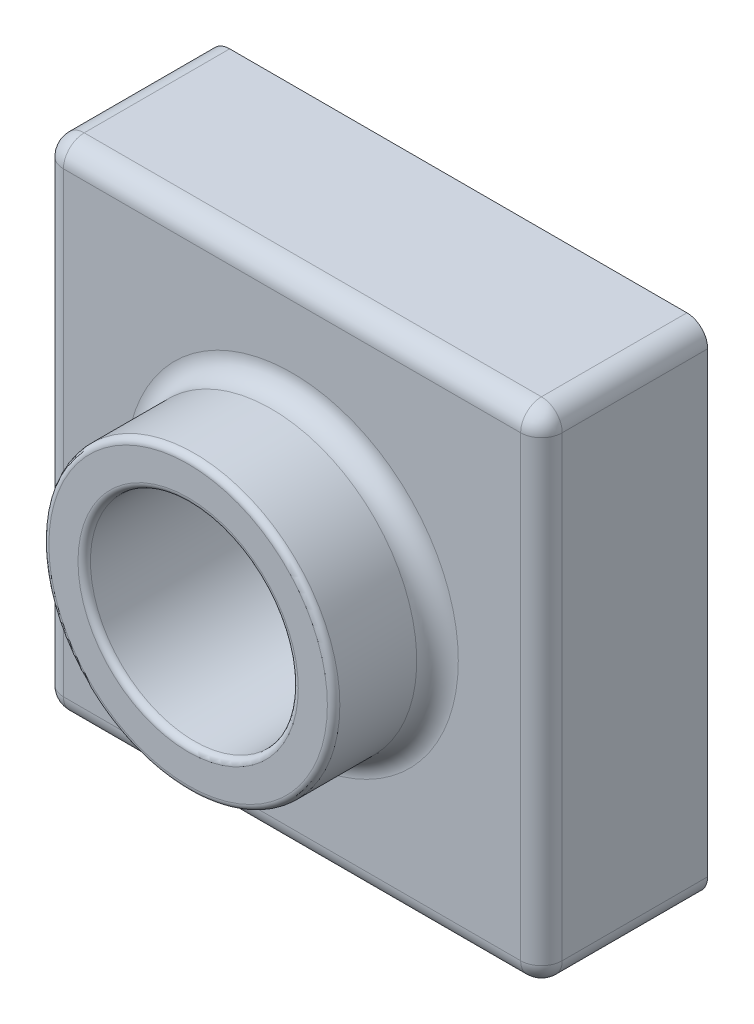
SolidWorks part; units mm, degrees
ref_plane "Front Plane" through (0, 0, 0) normal (0, 0, 1) x (1, 0, 0)
ref_plane "Top Plane" through (0, 0, 0) normal (0, 1, 0) x (1, 0, 0)
ref_plane "Right Plane" through (0, 0, 0) normal (1, 0, 0) x (0, 0, -1)
sketch "Sketch2" plane through (0, 0, 0) normal (0, 0, 1) x (1, 0, 0)
  line L1 (-60, -60) -> (60, -60)
  line L2 (-60, -60) -> (-60, 60)
  line L3 (-60, 60) -> (60, 60)
  line L4 (60, -60) -> (60, 60)
  line L5 (-60, -60) -> (60, 60) construction
  line L6 (-60, 60) -> (60, -60) construction
  point P0 (0, 0)
  dimension "D1" = 120
  dimension "D2" = 120
extrude "Boss-Extrude1" add sketch "Sketch2" along normal blind 40
sketch "Sketch3" plane through (0, 0, 40) normal (0, 0, 1) x (1, 0, 0)
  circle A0 centre (0, 0) radius 35
  dimension "D1" = 70
extrude "Boss-Extrude2" add sketch "Sketch3" along normal blind 25
sketch "Sketch4" plane through (0, 0, 65) normal (0, 0, 1) x (1, 0, 0)
  circle A0 centre (0, 0) radius 25
  dimension "D1" = 50
extrude "Cut-Extrude1" cut sketch "Sketch4" against normal through all
fillet "Fillet1" radius 5 9 edges at (0, -60, 40) (-60, 0, 40) (0, 60, 40) (60, 0, 40) (35, 0, 40) (-60, 60, 20) (60, 60, 20) (60, -60, 20) (-60, -60, 20)
fillet "Fillet2" radius 1.5 2 edges at (35, 0, 65) (25, 0, 65)
shell "Shell1" thickness 2 removed face at (25, 0, 0)
